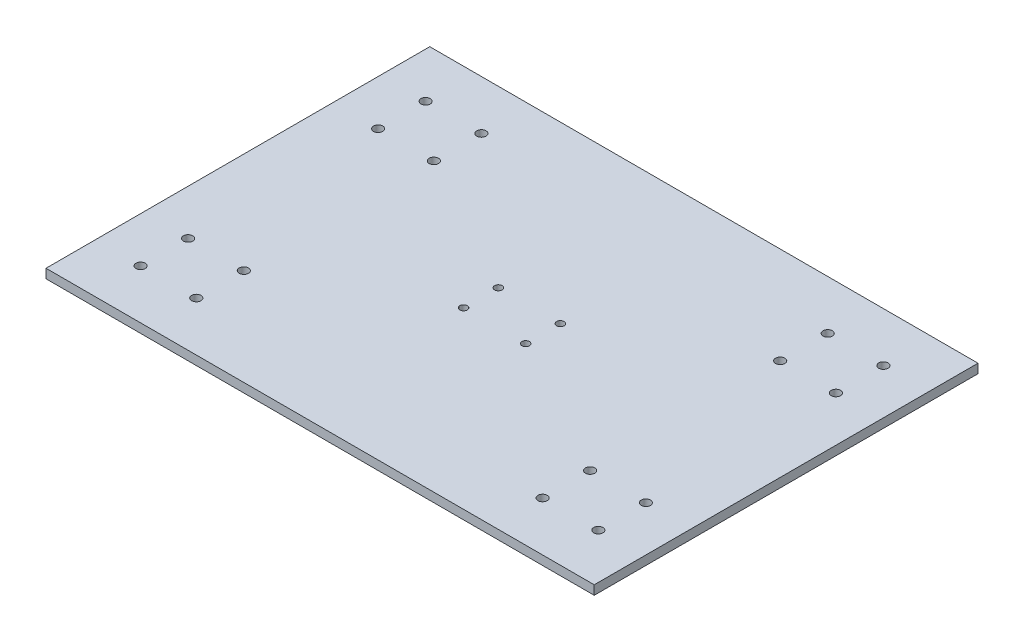
SolidWorks part; units mm, degrees
ref_plane "Front Plane" through (0, 0, 0) normal (0, 0, 1) x (1, 0, 0)
ref_plane "Top Plane" through (0, 0, 0) normal (0, 1, 0) x (1, 0, 0)
ref_plane "Right Plane" through (0, 0, 0) normal (1, 0, 0) x (0, 0, -1)
sketch "Sketch1" plane through (0, 0, 0) normal (0, 1, 0) x (1, 0, 0)
  line L1 (-150, -105) -> (150, -105)
  line L2 (-150, -105) -> (-150, 105)
  line L3 (-150, 105) -> (150, 105)
  line L4 (150, -105) -> (150, 105)
  line L5 (-150, -105) -> (150, 105) construction
  line L6 (-150, 105) -> (150, -105) construction
  point P0 (0, 0)
  dimension "D1" = 300
  dimension "D2" = 210
extrude "Boss-Extrude1" add sketch "Sketch1" along normal mid plane 5
sketch "Sketch2" plane through (0, 2.5, 0) normal (0, 1, 0) x (1, 0, 0)
  line L5 (-110, 105) -> (-110, -105)
  line L6 (-110, 105) -> (-110, -105) construction
  line L8 (110, -105) -> (110, 105)
  line L9 (110, -105) -> (110, 105) construction
  line L11 (150, 65) -> (-150, 65)
  line L12 (150, 65) -> (-150, 65) construction
  line L14 (-150, -65) -> (150, -65)
  line L15 (-150, -65) -> (150, -65) construction
  line L16 (-125.25, 78) -> (-94.75, 78) construction
  line L17 (-125.25, 78) -> (-125.25, 52) construction
  line L18 (-125.25, 52) -> (-94.75, 52) construction
  line L19 (-94.75, 78) -> (-94.75, 52) construction
  line L20 (-125.25, 78) -> (-94.75, 52) construction
  line L21 (-125.25, 52) -> (-94.75, 78) construction
  line L22 (94.75, 52) -> (125.25, 52) construction
  line L23 (94.75, 52) -> (94.75, 78) construction
  line L24 (94.75, 78) -> (125.25, 78) construction
  line L25 (125.25, 52) -> (125.25, 78) construction
  line L26 (94.75, 52) -> (125.25, 78) construction
  line L27 (94.75, 78) -> (125.25, 52) construction
  line L28 (94.75, -52) -> (125.25, -52) construction
  line L29 (94.75, -52) -> (94.75, -78) construction
  line L30 (94.75, -78) -> (125.25, -78) construction
  line L31 (125.25, -52) -> (125.25, -78) construction
  line L32 (94.75, -52) -> (125.25, -78) construction
  line L33 (94.75, -78) -> (125.25, -52) construction
  line L34 (-125.25, -78) -> (-94.75, -78) construction
  line L35 (-125.25, -78) -> (-125.25, -52) construction
  line L36 (-125.25, -52) -> (-94.75, -52) construction
  line L37 (-94.75, -78) -> (-94.75, -52) construction
  line L38 (-125.25, -78) -> (-94.75, -52) construction
  line L39 (-125.25, -52) -> (-94.75, -78) construction
  circle A0 centre (-125.25, 78) radius 2.55
  circle A1 centre (-125.25, 52) radius 2.55
  circle A2 centre (-94.75, 78) radius 2.55
  circle A3 centre (-94.75, 52) radius 2.55
  circle A4 centre (-125.25, -52) radius 2.55
  circle A5 centre (-125.25, -78) radius 2.55
  circle A6 centre (-94.75, -78) radius 2.55
  circle A7 centre (-94.75, -52) radius 2.55
  circle A8 centre (125.25, -52) radius 2.55
  circle A9 centre (94.75, -52) radius 2.55
  circle A10 centre (94.75, -78) radius 2.55
  circle A11 centre (125.25, -78) radius 2.55
  circle A12 centre (94.75, 78) radius 2.55
  circle A13 centre (94.75, 52) radius 2.55
  circle A14 centre (125.25, 78) radius 2.55
  circle A15 centre (125.25, 52) radius 2.55
  point P0 (-110, 65)
  point P13 (110, 65)
  point P18 (110, -65)
  point P23 (-110, -65)
  dimension "D13" = 5.1
  dimension "D14" = 5.1
  dimension "D15" = 5.1
  dimension "D16" = 5.1
  dimension "D17" = 5.1
  dimension "D18" = 5.1
  dimension "D19" = 5.1
  dimension "D20" = 5.1
  dimension "D21" = 5.1
  dimension "D22" = 5.1
  dimension "D23" = 5.1
  dimension "D24" = 5.1
  dimension "D25" = 5.1
  dimension "D26" = 5.1
  dimension "D27" = 5.1
  dimension "D28" = 5.1
  dimension "D1" = 40
  dimension "D5" = 30.5
  dimension "D6" = 26
  dimension "D7" = 30.5
  dimension "D8" = 26
  dimension "D9" = 26
  dimension "D10" = 30.5
  dimension "D11" = 26
  dimension "D12" = 30.5
  dimension "D2" = 40
  dimension "D3" = 40
  dimension "D4" = 40
extrude "Cut-Extrude1" cut sketch "Sketch2" against normal through all
sketch "Sketch3" plane through (0, 2.5, 0) normal (0, 1, 0) x (1, 0, 0)
  line L1 (-17, -9.5) -> (17, -9.5) construction
  line L2 (-17, -9.5) -> (-17, 9.5) construction
  line L3 (-17, 9.5) -> (17, 9.5) construction
  line L4 (17, -9.5) -> (17, 9.5) construction
  line L5 (-17, -9.5) -> (17, 9.5) construction
  line L6 (-17, 9.5) -> (17, -9.5) construction
  circle A0 centre (-17, 9.5) radius 2.05
  circle A1 centre (17, 9.5) radius 2.05
  circle A2 centre (17, -9.5) radius 2.05
  circle A3 centre (-17, -9.5) radius 2.05
  point P0 (0, 0)
  dimension "D3" = 4.1
  dimension "D4" = 4.1
  dimension "D5" = 4.1
  dimension "D6" = 4.1
  dimension "D1" = 34
  dimension "D2" = 19
extrude "Cut-Extrude2" cut sketch "Sketch3" against normal through all
